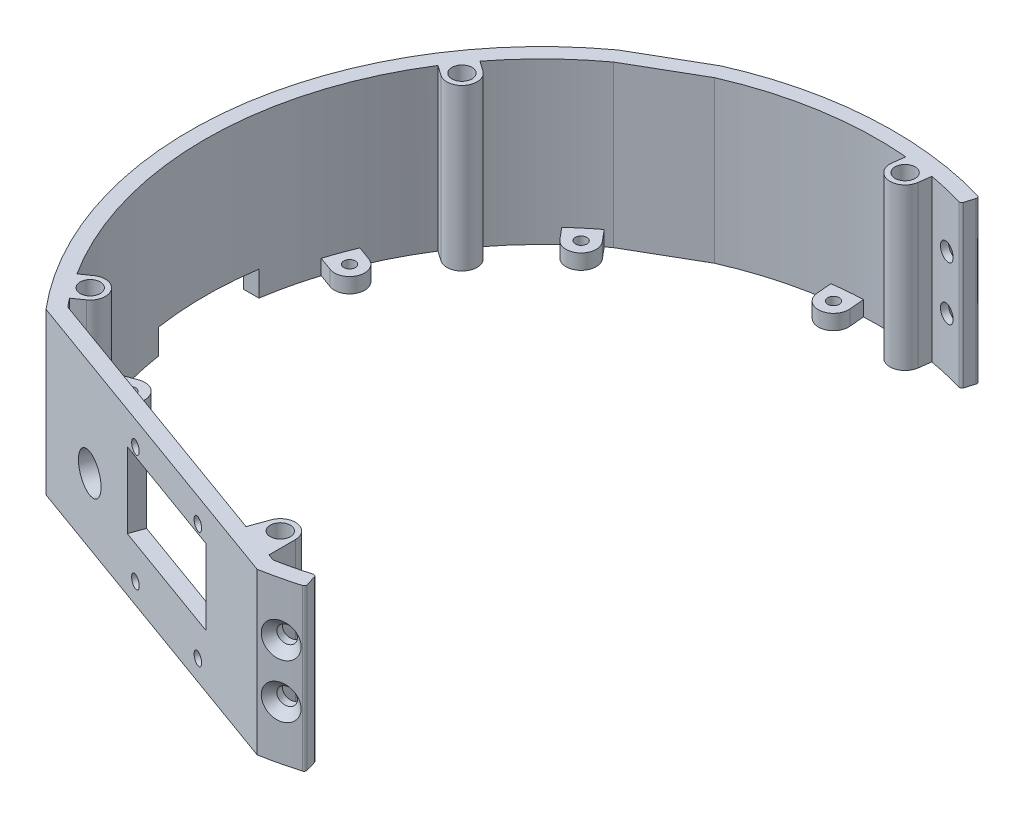
SolidWorks part; units mm, degrees
ref_plane "Front Plane" through (0, 0, 0) normal (0, 0, 1) x (1, 0, 0)
ref_plane "Top Plane" through (0, 0, 0) normal (0, 1, 0) x (1, 0, 0)
ref_plane "Right Plane" through (0, 0, 0) normal (1, 0, 0) x (0, 0, -1)
sketch "Sketch2" plane through (0, 0, 0) normal (0, 1, 0) x (1, 0, 0)
  line L0 (12.3, 68.9109) -> (12.3, -68.9109) construction
  line L1 (12.3, -68.9109) -> (-53.5286, -45.1076)
  line L2 (-28.3033, 64.0228) -> (-41.2937, 56.5228)
  line L3 (-51.7436, -42.5629) -> (12.3, -65.7208)
  line L4 (20.0782, 67.0587) -> (0, 0) construction
  line L5 (0, 0) -> (20.0782, -67.0587) construction
  line L6 (19.2177, 64.1847) -> (20.0782, 67.0587)
  line L7 (20.0782, -67.0587) -> (19.178, -64.0524)
  line L8 (-39.6526, 54.0062) -> (-26.9445, 61.3433)
  line L9 (-34.7985, 60.2728) -> (0, 0) construction
  line L10 (0, 0) -> (0, 50000) construction
  arc A0 (12.3, 68.9109) -> (-28.3033, 64.0228) centre (0, 0) ccw construction
  arc A1 (-53.5286, -45.1076) -> (-41.2937, 56.5228) centre (0, 0) cw
  arc A2 (12.3, 65.8613) -> (-26.9445, 61.3433) centre (0, 0) ccw
  arc A3 (12.3, 68.9109) -> (20.0782, 67.0587) centre (0, 0) cw
  arc A4 (12.3, 65.8613) -> (19.2177, 64.1847) centre (0, 0) cw
  arc A5 (12.3, -68.9109) -> (20.0782, -67.0587) centre (0, 0) ccw
  arc A6 (12.3, -65.7208) -> (19.178, -64.0524) centre (0, 0) ccw
  arc A7 (-39.6526, 54.0062) -> (-51.7436, -42.5629) centre (0, 0) ccw
  arc A8 (-41.2937, 56.5228) -> (12.3, -68.9109) centre (0, 0) ccw construction
  arc A9 (-28.3033, 64.0228) -> (12.3, 68.9109) centre (0, 0) cw
  point P18 (-33.2985, 57.6747)
  dimension "D1" = 70
  dimension "D4" = 3
  dimension "D6" = 8
  dimension "D2" = 12.3
  dimension "D3" = 3
  dimension "D5" = 70
  dimension "D7" = 8
  dimension "D8" = 3
  dimension "D9" = 15
  dimension "D10" = 30
extrude "Boss-Extrude1" add sketch "Sketch2" along normal blind 32
sketch "Sketch3" plane through (0, 0, 0) normal (0, 1, 0) x (1, 0, 0)
  line L0 (12.3, 68.9109) -> (12.3, -68.9109) construction
  line L1 (20.0782, -67.0587) -> (19.178, -64.0524) construction
  line L2 (19.2177, 64.1847) -> (20.0782, 67.0587) construction
  circle A0 centre (0, 0) radius 70 construction
  arc A1 (12.3, -68.9109) -> (20.0782, -67.0587) centre (0, 0) ccw
  arc A2 (12.3, 68.9109) -> (20.0782, 67.0587) centre (0, 0) cw
  point P8 (16.2155, -68.0959)
  point P9 (16.2155, 68.0959)
  dimension "D2" = 140
  dimension "D1" = 12.3
sketch3d "3DSketch1"
  line L0 (16.2155, 0, 68.0959) -> (16.2155, 32, 68.0959)
  line L1 (16.2155, 0, -68.0959) -> (16.2155, 32, -68.0959)
  arc A0 (12.3, 32, 68.9109) -> (20.0782, 32, 67.0587) centre (0, 32, 0) ccw construction
  arc A1 (20.0782, 32, -67.0587) -> (-28.3033, 32, -64.0228) centre (0, 32, 0) ccw construction
  point P6 (0, 102, 0)
  point P13 (0, 102, 0)
  point P14 (16.2155, 21.3333, 68.0959)
  point P15 (16.2155, 10.6667, 68.0959)
  point P16 (16.2155, 10.6667, -68.0959)
  point P17 (16.2155, 21.3333, -68.0959)
  dimension "D1" = 10.6667
  dimension "D2" = 21.3333
  dimension "D3" = 10.6667
  dimension "D4" = 21.3333
ref_plane "Plane1" through (16.2155, 0, -68.0959) normal (0.2317, 0, -0.9728) x (-0.9728, 0, -0.2317)
ref_plane "Plane2" through (16.2155, 0, 68.0959) normal (0.2317, 0, 0.9728) x (0.9728, 0, -0.2317)
sketch "Sketch4" plane through (16.2155, 0, -68.0959) normal (0.2317, 0, -0.9728) x (-0.9728, 0, -0.2317)
  line L0 (0, 0) -> (0, 32) construction
  circle A0 centre (0, 21.3333) radius 1.65 construction
  circle A1 centre (0, 10.6667) radius 1.65 construction
  point P0 (0, 21.3333)
  point P4 (0, 10.6667)
  dimension "D1" = 3.3
  dimension "D2" = 10.6667
  dimension "D3" = 21.3333
sketch "Sketch5" plane through (16.2155, 0, 68.0959) normal (0.2317, 0, 0.9728) x (0.9728, 0, -0.2317)
  line L0 (0, 0) -> (0, 32) construction
  circle A0 centre (0, 21.3333) radius 1.65 construction
  circle A1 centre (0, 10.6667) radius 1.65 construction
  point P0 (0, 21.3333)
  point P4 (0, 10.6667)
  dimension "D1" = 3.3
  dimension "D2" = 10.6667
  dimension "D3" = 21.3333
fillet "Fillet1" radius 0.5 4 edges at (20.0782, 16, -67.0587) (19.2177, 16, -64.1847) (19.178, 16, 64.0524) (20.0782, 16, 67.0587)
sketch "Sketch6" plane through (0, 0, 0) normal (1, 0, 0) x (0, 0, -1)
  line L0 (70, 0) -> (-70, 0) construction
  line L1 (-10, 0) -> (10, 0)
  line L2 (-10, 0) -> (-10, 5)
  line L3 (-10, 5) -> (10, 5)
  line L4 (10, 0) -> (10, 5)
  dimension "D1" = 10
  dimension "D2" = 5
  dimension "D3" = 20
extrude "Cut-Extrude3" cut sketch "Sketch6" against normal through all
sketch "Sketch7" plane through (-20.6143, 0, 57.0092) normal (-0.34, 0, 0.9404) x (0.9404, 0, 0.34)
  line L0 (5, 29.3) -> (5, 2) construction
  line L1 (-8.65, 29.3) -> (18.65, 29.3) construction
  line L2 (-8.65, 29.3) -> (-8.65, 2) construction
  line L3 (-8.65, 2) -> (18.65, 2) construction
  line L4 (18.65, 29.3) -> (18.65, 2) construction
  line L5 (-8.65, 29.3) -> (18.65, 2) construction
  line L6 (-8.65, 2) -> (18.65, 29.3) construction
  line L7 (-35, 0) -> (35, 0) construction
  line L8 (-8.05, 25.58) -> (18.05, 25.58)
  line L9 (-8.05, 25.58) -> (-8.05, 10.58)
  line L10 (-8.05, 10.58) -> (18.05, 10.58)
  line L11 (18.05, 25.58) -> (18.05, 10.58)
  line L12 (-8.05, 25.58) -> (18.05, 10.58) construction
  line L13 (-8.05, 10.58) -> (18.05, 25.58) construction
  line L14 (-5.35, 27.25) -> (15.35, 27.25) construction
  line L15 (-5.35, 27.25) -> (-5.35, 4.05) construction
  line L16 (-5.35, 4.05) -> (15.35, 4.05) construction
  line L17 (15.35, 27.25) -> (15.35, 4.05) construction
  line L18 (70, 0) -> (-70, 0) construction
  circle A0 centre (-5.35, 27.25) radius 1.25
  circle A1 centre (15.35, 27.25) radius 1.25
  circle A2 centre (15.35, 4.05) radius 1.25
  circle A3 centre (-5.35, 4.05) radius 1.25
  circle A4 centre (-20.5, 13) radius 3.75
  point P0 (5, 15.65)
  point P5 (5, 18.08)
  point P24 (0, 0)
  dimension "D9" = 2.5
  dimension "D13" = 7.5
  dimension "D14" = 13
  dimension "D15" = 20.5
  dimension "D1" = 27.3
  dimension "D2" = 27.3
  dimension "D3" = 26.1
  dimension "D4" = 15
  dimension "D5" = 2.05
  dimension "D6" = 3.3
  dimension "D7" = 20.7
  dimension "D8" = 11.22
  dimension "D10" = 5
  dimension "D11" = 2
  dimension "D12" = 23.2
extrude "Cut-Extrude4" cut sketch "Sketch7" against normal blind 8
sketch "Sketch8" plane through (0, 0, 0) normal (0, 1, 0) x (1, 0, 0)
  line L0 (8.7453, 66.4268) -> (8.4189, 63.9482) construction
  line L1 (11.7108, 65.9686) -> (11.3933, 63.5566)
  line L2 (5.7621, 66.7518) -> (5.4446, 64.3398)
  line L3 (5.4446, 64.3398) -> (11.3933, 63.5566) construction
  line L4 (-54.8832, 38.4296) -> (-52.8353, 36.9957) construction
  line L5 (-53.1074, 40.8485) -> (-51.1146, 39.4531)
  line L6 (-56.5489, 35.9336) -> (-54.556, 34.5382)
  line L7 (-54.556, 34.5382) -> (-51.1146, 39.4531) construction
  line L8 (-54.8832, -38.4296) -> (-52.8353, -36.9957) construction
  line L9 (-56.5489, -35.9336) -> (-54.556, -34.5382)
  line L10 (-53.1074, -40.8485) -> (-51.1146, -39.4531)
  line L11 (-51.1146, -39.4531) -> (-54.556, -34.5382) construction
  line L12 (0, 1.3173) -> (0, 50001.3173) construction
  line L13 (11, -65.2507) -> (11, -60)
  line L14 (12.3, -65.7208) -> (-51.7436, -42.5629) construction
  line L15 (5.1788, -58.9799) -> (3.8466, -62.6641)
  line L16 (8, -60) -> (6.6678, -63.6842) construction
  line L17 (11, -65.2507) -> (3.8466, -62.6641)
  arc A0 (-53.1074, -40.8485) -> (-56.5489, -35.9336) centre (0, 0) cw
  arc A1 (18.7417, 64.3253) -> (-26.9445, 61.3433) centre (0, 0) ccw construction
  arc A2 (5.7621, 66.7518) -> (11.7108, 65.9686) centre (0, 0) cw
  circle A3 centre (8.4189, 63.9482) radius 1.65
  arc A4 (11.3933, 63.5566) -> (5.4446, 64.3398) centre (8.4189, 63.9482) cw
  arc A5 (-56.5489, 35.9336) -> (-53.1074, 40.8485) centre (0, 0) cw
  circle A6 centre (-52.8353, 36.9957) radius 1.65
  arc A7 (-51.1146, 39.4531) -> (-54.556, 34.5382) centre (-52.8353, 36.9957) cw
  circle A8 centre (-52.8353, -36.9957) radius 1.65
  arc A9 (-54.556, -34.5382) -> (-51.1146, -39.4531) centre (-52.8353, -36.9957) cw
  arc A10 (11, -60) -> (5.1788, -58.9799) centre (8, -60) ccw
  circle A11 centre (8, -60) radius 1.65
  circle A12 centre (0, 0) radius 67 construction
  point P12 (8.7453, 66.4268)
  point P15 (8.7453, 66.4268)
  point P17 (8.4189, 63.9482)
  point P24 (-54.8832, 38.4296)
  point P26 (-54.8832, 38.4296)
  point P27 (-52.8353, 36.9957)
  point P43 (-52.8353, -36.9957)
  dimension "D1" = 3.3
  dimension "D2" = 6
  dimension "D3" = 3.3
  dimension "D5" = 3.3
  dimension "D13" = 3
  dimension "D14" = 3.3
  dimension "D4" = 6
  dimension "D6" = 6
  dimension "D7" = 2.5
  dimension "D8" = 7.5
  dimension "D9" = 55
  dimension "D10" = 55
  dimension "D11" = 2.5
  dimension "D12" = 2.5
  dimension "D15" = 60
  dimension "D16" = 8
extrude "Boss-Extrude2" add sketch "Sketch8" along normal up to surface (32 mm away) up to face at (-6.541, 32, -1.7)
sketch "Sketch13" plane through (0, 0, 0) normal (0, 1, 0) x (1, 0, 0)
  line L0 (-62.8963, 22.8924) -> (-60.0772, 21.8663) construction
  line L1 (-59.0511, 24.6854) -> (-61.1032, 19.0472) construction
  line L2 (-61.1032, 19.0472) -> (-63.9223, 20.0733)
  line L3 (-61.8702, 25.7114) -> (-59.0511, 24.6854)
  line L4 (0, 0) -> (0, 50000) construction
  line L5 (-62.8963, -22.8924) -> (-60.0772, -21.8663) construction
  line L6 (-61.1032, -19.0472) -> (-59.0511, -24.6854) construction
  line L7 (-59.0511, -24.6854) -> (-61.8702, -25.7114)
  line L8 (-63.9223, -20.0733) -> (-61.1032, -19.0472)
  line L9 (-5.8336, 66.6781) -> (-5.5721, 63.6895) construction
  line L10 (-2.5835, 63.951) -> (-8.5607, 63.4281) construction
  line L11 (-8.5607, 63.4281) -> (-8.8222, 66.4166)
  line L12 (-2.845, 66.9396) -> (-2.5835, 63.951)
  line L13 (-43.0236, 51.2735) -> (-41.0952, 48.9754) construction
  line L14 (-38.7971, 50.9037) -> (-43.3933, 47.047) construction
  line L15 (-43.3933, 47.047) -> (-45.3217, 49.3451)
  line L16 (-40.7254, 53.2019) -> (-38.7971, 50.9037)
  line L17 (1.0254, -61.6439) -> (2.0455, -58.8227) construction
  line L18 (-0.7757, -57.8026) -> (4.8667, -59.8428) construction
  line L19 (4.8667, -59.8428) -> (3.8466, -62.6641)
  line L20 (-1.7959, -60.6238) -> (-0.7757, -57.8026)
  line L21 (3.8466, -62.6641) -> (-1.7959, -60.6238)
  line L22 (5.1788, -58.9799) -> (3.8466, -62.6641) construction
  line L25 (3.8466, -62.6641) -> (-51.7436, -42.5629) construction
  circle A0 centre (0, 0) radius 67 construction
  arc A1 (-63.9223, 20.0733) -> (-61.8702, 25.7114) centre (0, 0) cw
  arc A2 (-61.1032, 19.0472) -> (-59.0511, 24.6854) centre (-60.0772, 21.8663) ccw
  circle A3 centre (-60.0772, 21.8663) radius 1.15
  arc A4 (-61.8702, -25.7114) -> (-63.9223, -20.0733) centre (0, 0) cw
  arc A5 (-59.0511, -24.6854) -> (-61.1032, -19.0472) centre (-60.0772, -21.8663) ccw
  circle A6 centre (-60.0772, -21.8663) radius 1.15
  arc A7 (-8.8222, 66.4166) -> (-2.845, 66.9396) centre (0, 0) cw
  arc A8 (-8.5607, 63.4281) -> (-2.5835, 63.951) centre (-5.5721, 63.6895) ccw
  circle A9 centre (-5.5721, 63.6895) radius 1.15
  arc A10 (-45.3217, 49.3451) -> (-40.7254, 53.2019) centre (0, 0) cw
  arc A11 (-43.3933, 47.047) -> (-38.7971, 50.9037) centre (-41.0952, 48.9754) ccw
  circle A12 centre (-41.0952, 48.9754) radius 1.15
  arc A14 (4.8667, -59.8428) -> (-0.7757, -57.8026) centre (2.0455, -58.8227) ccw
  circle A15 centre (2.0455, -58.8227) radius 1.15
  point P10 (-60.0772, 21.8663)
  point P20 (-60.0772, -21.8663)
  point P30 (-5.5721, 63.6895)
  point P41 (-41.0952, 48.9754)
  point P52 (2.0455, -58.8227)
  dimension "D1" = 134
  dimension "D2" = 3
  dimension "D3" = 2.3
  dimension "D6" = 3
  dimension "D7" = 2.3
  dimension "D10" = 3
  dimension "D11" = 2.3
  dimension "D14" = 3
  dimension "D15" = 2.3
  dimension "D18" = 3
  dimension "D19" = 2.3
  dimension "D4" = 3
  dimension "D5" = 70
  dimension "D8" = 3
  dimension "D9" = 70
  dimension "D12" = 3
  dimension "D13" = 5
  dimension "D16" = 3
  dimension "D17" = 40
  dimension "D20" = 3
  dimension "D21" = 2.0455
  dimension "D22" = 58.8227
extrude "Boss-Extrude3" add sketch "Sketch13" along normal blind 3
hole_wizard "CSK for M3 Flat Head Machine Screw1" positions "Sketch4" profile "Sketch16" countersink size "M3" standard "ANSI Metric"
sketch "Sketch16" plane through (16.2155, 21.3333, -68.0959) normal (0, 1, 0) x (-0.9728, 0, -0.2317)
  line L0 (0, 0) -> (0, 21.0215)
  line L1 (0, 21.0215) -> (1.7, 20)
  line L2 (1.7, 20) -> (1.7, 1.675)
  line L3 (1.7, 1.675) -> (3.375, 0)
  line L5 (3.375, 0) -> (0, 0)
  line L6 (-1.7, 1.675) -> (-3.375, 0) construction
  line L10 (0, 21.0215) -> (-1.7, 20) construction
  line L11 (0, -6.35) -> (0, 107.95) construction
  dimension "Hole Dia." = 3.4
  dimension "Hole Depth" = 20
  dimension "Near C'Sink Dia." = 6.75
  dimension "Near C'Sink Angle" = 90
  dimension "Drill Angle" = 118
hole_wizard "CSK for M3 Flat Head Machine Screw2" positions "Sketch5" profile "Sketch17" countersink size "M3" standard "ANSI Metric"
sketch "Sketch17" plane through (16.2155, 21.3333, 68.0959) normal (0, 1, 0) x (0.9728, 0, -0.2317)
  line L0 (0, 0) -> (0, 21.0215)
  line L1 (0, 21.0215) -> (1.7, 20)
  line L2 (1.7, 20) -> (1.7, 1.675)
  line L3 (1.7, 1.675) -> (3.375, 0)
  line L5 (3.375, 0) -> (0, 0)
  line L6 (-1.7, 1.675) -> (-3.375, 0) construction
  line L10 (0, 21.0215) -> (-1.7, 20) construction
  line L11 (0, -6.35) -> (0, 107.95) construction
  dimension "Hole Dia." = 3.4
  dimension "Hole Depth" = 20
  dimension "Near C'Sink Dia." = 6.75
  dimension "Near C'Sink Angle" = 90
  dimension "Drill Angle" = 118
sketch "Sketch18" plane through (0, 32, 0) normal (0, 1, 0) x (1, 0, 0)
  circle A0 centre (8.4189, 63.9482) radius 2
  circle A1 centre (-52.8353, 36.9957) radius 2
  circle A2 centre (-52.8353, -36.9957) radius 2
  circle A3 centre (8, -60) radius 2
  dimension "D1" = 4
extrude "Cut-Extrude5" cut sketch "Sketch18" against normal blind 4.78
